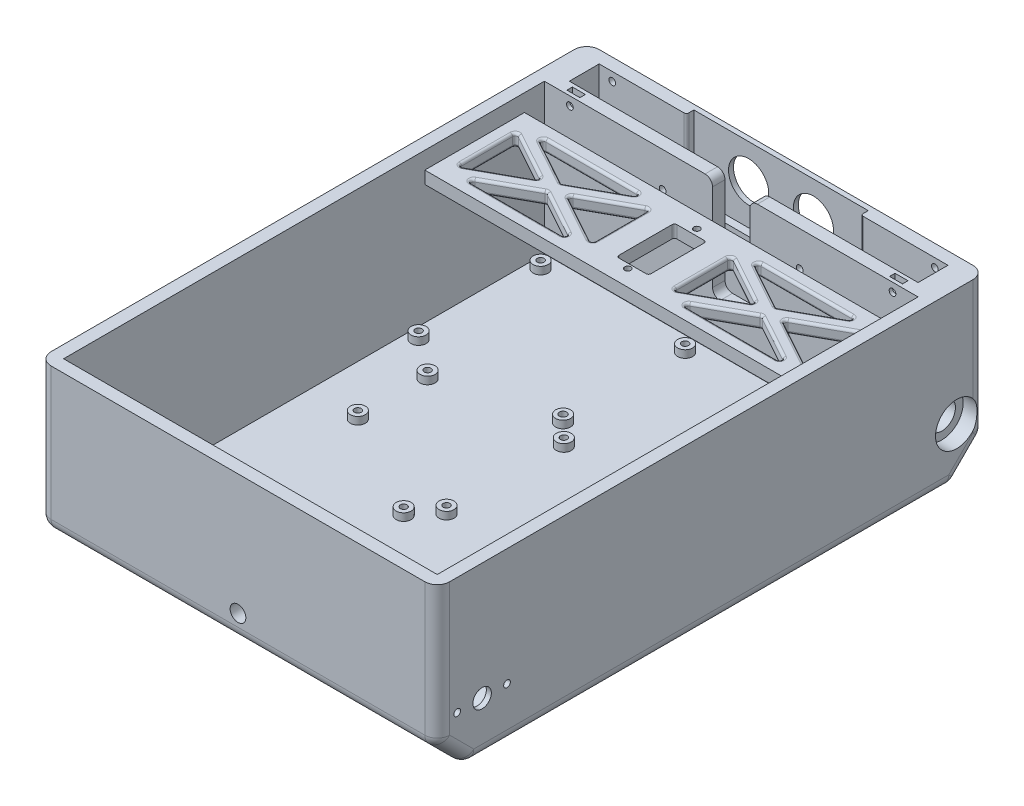
SolidWorks part; units mm, degrees
ref_plane "Front Plane" through (0, 0, 0) normal (0, 0, 1) x (1, 0, 0)
ref_plane "Top Plane" through (0, 0, 0) normal (0, 1, 0) x (1, 0, 0)
ref_plane "Right Plane" through (0, 0, 0) normal (1, 0, 0) x (0, 0, -1)
sketch "Main Body" plane through (0, 0, 0) normal (0, 1, 0) x (1, 0, 0)
  line L0 (-75, 110) -> (75, 110)
  line L1 (-75, -105) -> (75, -105)
  line L2 (-75, -105) -> (-75, 105)
  line L3 (-75, 105) -> (75, 105)
  line L4 (75, -105) -> (75, 105)
  line L5 (-75, -105) -> (75, 105) construction
  line L6 (-75, 105) -> (75, -105) construction
  line L7 (80, -105) -> (80, 105)
  line L8 (-75, -110) -> (75, -110)
  line L9 (-80, -105) -> (-80, 105)
  line L10 (-80, -110) -> (80, -110) construction
  line L11 (-80, -110) -> (-80, 110) construction
  line L12 (80, -110) -> (80, 110) construction
  line L13 (-80, 110) -> (80, 110) construction
  arc A0 (-75, -110) -> (-80, -105) centre (-75, -105) cw
  arc A1 (80, -105) -> (75, -110) centre (75, -105) cw
  arc A2 (75, 110) -> (80, 105) centre (75, 105) cw
  arc A3 (-75, 110) -> (-80, 105) centre (-75, 105) ccw
  point P0 (0, 0)
  dimension "D4" = 5
  dimension "D1" = 75
  dimension "D2" = 210
  dimension "D3" = 5
extrude "Boss-Extrude1" add sketch "Main Body" along normal blind 8 contours L1 L4 L3 L2 | L9 L8 L7 L0 L4 L1 L2 L3 region at (0, 0, -107.2797) region at (0, 0, 0)
extrude "Boss-Extrude3" add sketch "Main Body<4>" along normal blind 60 from surface starting at face at (0, 8, 0)
sketch "Main Body<4>" plane through (0, 0, 0) normal (0, 1, 0) x (1, 0, 0) same geometry as "Main Body"
sketch "Sketch1" plane through (75, 0, 0) normal (-1, 0, 0) x (0, 0, 1)
  line L0 (105, 68) -> (105, 8) construction
  line L1 (-105, 8) -> (105, 8) construction
  line L2 (79, 15.5) -> (105, 15.5)
  line L3 (79, 8) -> (105, 8)
  line L4 (79, 8) -> (79, 34)
  line L5 (79, 34) -> (105, 34)
  line L6 (105, 8) -> (105, 34)
  line L7 (79, 8) -> (105, 34) construction
  line L8 (79, 34) -> (105, 8) construction
  circle A0 centre (92, 21) radius 13
  line M2 (-105, 8) -> (105, 8)
  line M3 (105, 8) -> (105, 68)
  dimension "D1" = 26
  dimension "D2" = 7.5
extrude "Boss-Extrude4" add sketch "Sketch1" along normal up to surface (150 mm away) contours A0 L4 M2 | A0 L3 M3 region at (75, 10.5201, 82.0674) region at (75, 10.5201, 101.9326) up to face at (-75, 38, 0)
sketch "Sketch2" plane through (0, 0, 0) normal (1, 0, 0) x (0, 0, -1)
  line L0 (-105, 68) -> (-105, 15.5) construction
  line L1 (-105, 8) -> (-79, 8)
  line L2 (-105, 8) -> (-105, 15.5)
  line L3 (-105, 15.5) -> (-79, 15.5)
  line L4 (-79, 8) -> (-79, 15.5)
  line L5 (105, 8) -> (-79, 8) construction
  line L6 (-79, 8) -> (-79, 15.5) construction
  line L7 (-79, 15.5) -> (-80.2208, 15.5) construction
extrude "Cut-Extrude1" cut sketch "Sketch2" against normal mid plane 12
sketch "Sketch3" plane through (0, 8, 0) normal (0, 1, 0) x (1, 0, 0)
  line L0 (75, -105) -> (-75, -105) construction
  line L1 (-4, -79) -> (-11, -79)
  line L2 (-4, -79) -> (-4, -105)
  line L3 (-4, -105) -> (-11, -105)
  line L4 (-11, -79) -> (-11, -105)
  line L5 (0, 0) -> (0, -105) construction
  line L6 (-75, -79) -> (-6, -79) construction
  line L7 (11, -79) -> (11, -105)
  line L8 (4, -105) -> (11, -105)
  line L9 (4, -79) -> (4, -105)
  line L10 (4, -79) -> (11, -79)
  line L11 (-6, -103.7792) -> (-6, -92) construction
  dimension "D1" = 5
  dimension "D2" = 4
extrude "Boss-Extrude5" add sketch "Sketch3" along normal blind 20
sketch "Sketch4" plane through (0, 8, 0) normal (0, 1, 0) x (1, 0, 0)
  line L0 (-75, -105) -> (-75, 105) construction
  line L1 (-75, 93) -> (75, 93)
  line L2 (-75, 93) -> (-75, 88)
  line L3 (-75, 88) -> (75, 88)
  line L4 (75, 93) -> (75, 88)
  line L5 (75, 105) -> (75, -105) construction
  line L6 (-75, 105) -> (75, 105) construction
  dimension "D1" = 17
  dimension "D2" = 5
extrude "Boss-Extrude6" add sketch "Sketch4" along normal up to surface (60 mm away) up to face at (0, 68, 0)
sketch "Sketch5" plane through (80, 0, 0) normal (1, 0, 0) x (0, 0, -1)
  circle A0 centre (-92, 21) radius 3.5 construction
  circle A1 centre (-92, 21) radius 3.5
  circle A2 centre (-92, 21) radius 3.7
  dimension "D1" = 0.2
extrude "Cut-Extrude4" cut sketch "Sketch5" against normal up to next contours A1 | A2 A1 region at (80, 21, 92) region at (80, 21, 95.5953)
sketch "Sketch6" plane through (-75, 0, 0) normal (1, 0, 0) x (0, 0, -1)
  circle A0 centre (-92, 21) radius 13
  dimension "D1" = 26
extrude "Cut-Extrude5" cut sketch "Sketch6" against normal offset from surface (3 mm away) 2 up to face at (-80, 34, 0)
mirror "Mirror1" about plane through (0, 0, 0) normal (1, 0, 0) of "Cut-Extrude4"
sketch "Sketch8" plane through (75, 0, 0) normal (-1, 0, 0) x (0, 0, 1)
  circle A0 centre (92, 21) radius 13
  dimension "D1" = 26
extrude "Cut-Extrude6" cut sketch "Sketch8" against normal offset from surface (3 mm away) 2 up to face at (80, 21, 88.3)
sketch "Sketch10" plane through (80, 0, 0) normal (1, 0, 0) x (0, 0, -1)
  circle A1 centre (-82, 21) radius 1.25
  circle A2 centre (-82, 21) radius 1.25
  circle A3 centre (-102, 21) radius 1.25
  circle A4 centre (-102, 21) radius 1.25
  circle A5 centre (-92, 21) radius 12.5
  circle A6 centre (-92, 21) radius 12.5
  circle A63 centre (-102, 21) radius 1.35
  circle A64 centre (-82, 21) radius 1.35
  dimension "D4" = 2.7
extrude "Cut-Extrude7" cut sketch "Sketch10" against normal up to next contours A2 | A64 A2 | A4 | A63 A4 region at (80, 21, 82) region at (80, 21, 102) region at (80, 21, 103.3118) region at (80, 21, 83.3118)
mirror "Mirror3" about plane through (0, 0, 0) normal (1, 0, 0) of "Cut-Extrude7"
sketch "Sketch11" plane through (80, 0, 0) normal (1, 0, 0) x (0, 0, -1)
  circle A0 centre (98.55, 21.05) radius 4.45 construction
  circle A1 centre (98.55, 21.05) radius 4.45
  circle A3 centre (98.55, 21.05) radius 5.45
  dimension "D1" = 1
extrude "Cut-Extrude10" cut sketch "Sketch11" against normal through all contours A1 | A3 A1 region at (80, 21.05, -98.55) region at (80, 21.05, -93.2541)
sketch "Sketch12" plane through (-75, 0, 0) normal (1, 0, 0) x (0, 0, -1)
  line L0 (93, 8) -> (105, 8) construction
  line L1 (93, 68) -> (105, 68)
  line L2 (93, 68) -> (93, 8)
  line L3 (93, 8) -> (105, 8)
  line L4 (105, 68) -> (105, 8)
  line L6 (93, 68) -> (93, 8) construction
  line L7 (93, 68) -> (105, 68) construction
  circle A2 centre (98.55, 21.05) radius 5.45 construction
  circle A3 centre (98.55, 21.05) radius 5.45
extrude "Boss-Extrude7" add sketch "Sketch12" along normal blind 5
sketch "Sketch13" plane through (-80, 0, 0) normal (-1, 0, 0) x (0, 0, 1)
  circle A0 centre (-98.55, 21.05) radius 8.55
  circle A2 centre (-98.55, 21.05) radius 5.45 construction
  dimension "D1" = 17.1
extrude "Cut-Extrude11" cut sketch "Sketch13" against normal blind 6
mirror "Mirror4" about plane through (0, 0, 0) normal (1, 0, 0) of "Boss-Extrude7", "Cut-Extrude11"
sketch "Sketch14" plane through (0, 8, 0) normal (0, 1, 0) x (1, 0, 0)
  line L0 (-4, -105) -> (-4, -79) construction
  line L1 (-4, -95) -> (4, -95)
  line L2 (-4, -95) -> (-4, -105)
  line L3 (-4, -105) -> (4, -105)
  line L4 (4, -95) -> (4, -105)
  dimension "D1" = 10
extrude "Boss-Extrude9" add sketch "Sketch14" along normal blind 5
sketch "Sketch15" plane through (0, 0, 110) normal (0, 0, 1) x (1, 0, 0)
  arc A4 (3.15, 19.5) -> (-3.15, 19.5) centre (0, 19.5) ccw
  arc A5 (-3.15, 19.5) -> (3.15, 19.5) centre (0, 19.5) ccw
  arc A6 (3, 19.5) -> (-3, 19.5) centre (0, 19.5) ccw construction
  dimension "D1" = 3.15
extrude "Cut-Extrude12" cut sketch "Sketch15" against normal up to next contours A4 A5 region at (0, 19.5, 110)
sketch "Sketch16" plane through (0, 0, 0) normal (0, -1, 0) x (1, 0, 0)
  circle A0 centre (-12.5, -82) radius 1.475 construction
  circle A1 centre (-70.5, -82) radius 1.475 construction
  circle A2 centre (-70.5, -33) radius 1.475 construction
  circle A3 centre (-12.5, -33) radius 1.475 construction
  circle A4 centre (-4.2, -25) radius 1.475 construction
  circle A5 centre (-55, -21.12) radius 1.475 construction
  circle A6 centre (-55, 6.88) radius 1.475 construction
  circle A7 centre (-4.2, 22.08) radius 1.475 construction
  circle A8 centre (-12.3, 31.18) radius 1.475 construction
  circle A9 centre (24.2, 31.18) radius 1.475 construction
  circle A10 centre (37.8459, 24.117) radius 1.475 construction
  circle A11 centre (59.5541, 24.117) radius 1.475 construction
  circle A12 centre (59.5541, 68.243) radius 1.475 construction
  circle A13 centre (37.8459, 68.243) radius 1.475 construction
  circle A14 centre (24.2, 67.68) radius 1.475 construction
  circle A15 centre (-12.3, 67.68) radius 1.475 construction
  circle A16 centre (-12.5, -82) radius 1.475
  circle A17 centre (-70.5, -82) radius 1.475
  circle A18 centre (-70.5, -33) radius 1.475
  circle A19 centre (-12.5, -33) radius 1.475
  circle A20 centre (-4.2, -25) radius 1.475
  circle A21 centre (-55, -21.12) radius 1.475
  circle A22 centre (-55, 6.88) radius 1.475
  circle A23 centre (-4.2, 22.08) radius 1.475
  circle A24 centre (-12.3, 31.18) radius 1.475
  circle A25 centre (24.2, 31.18) radius 1.475
  circle A26 centre (37.8459, 24.117) radius 1.475
  circle A27 centre (59.5541, 24.117) radius 1.475
  circle A28 centre (59.5541, 68.243) radius 1.475
  circle A29 centre (37.8459, 68.243) radius 1.475
  circle A30 centre (24.2, 67.68) radius 1.475
  circle A31 centre (-12.3, 67.68) radius 1.475
  circle A32 centre (-70.5, -82) radius 1.35
  circle A33 centre (-12.5, -82) radius 1.35
  circle A34 centre (-12.5, -33) radius 1.35
  circle A35 centre (-4.2, -25) radius 1.35
  circle A36 centre (-55, -21.12) radius 1.35
  circle A37 centre (-70.5, -33) radius 1.35
  circle A38 centre (-55, 6.88) radius 1.35
  circle A39 centre (-12.3, 31.18) radius 1.35
  circle A40 centre (-4.2, 22.08) radius 1.35
  circle A41 centre (24.2, 31.18) radius 1.35
  circle A42 centre (37.8459, 24.117) radius 1.35
  circle A43 centre (59.5541, 24.117) radius 1.35
  circle A44 centre (37.8459, 68.243) radius 1.35
  circle A45 centre (59.5541, 68.243) radius 1.35
  circle A46 centre (24.2, 67.68) radius 1.35
  circle A47 centre (-12.3, 67.68) radius 1.35
  dimension "D1" = 2.7
extrude "Cut-Extrude13" cut sketch "Sketch16" against normal up to next contours A47 | A46 | A44 | A45 | A35 | A37 | A36 | A38 | A39 | A40 | A41 | A42 | A43 | A32 | A33 | A19 region at (-70.5, 0, -82) region at (-12.5, 0, -82) region at (-4.2, 0, -25) region at (-55, 0, -21.12) region at (-70.5, 0, -33) region at (-55, 0, 6.88) region at (-12.3, 0, 31.18) region at (-4.2, 0, 22.08) region at (24.2, 0, 31.18) region at (37.8459, 0, 24.117) region at (59.5541, 0, 24.117) region at (37.8459, 0, 68.243) region at (59.5541, 0, 68.243) region at (24.2, 0, 67.68) region at (-12.3, 0, 67.68)
sketch "Sketch18" plane through (75, 0, 0) normal (-1, 0, 0) x (0, 0, 1)
  line L1 (-80, 61.1) -> (-40, 61.1)
  line L2 (-80, 61.1) -> (-80, 56.1)
  line L3 (-80, 56.1) -> (-40, 56.1)
  line L4 (-40, 61.1) -> (-40, 56.1)
  line L5 (-88, 68) -> (105, 68) construction
  dimension "D1" = 5
  dimension "D2" = 30
  dimension "D3" = 40
  dimension "D4" = 6.9
extrude "Boss-Extrude11" add sketch "Sketch18" along normal up to next
sketch "Sketch19" plane through (0, 68, 0) normal (0, 1, 0) x (1, 0, 0)
  line L1 (-6.425, 71.625) -> (6.425, 71.625)
  line L2 (-6.425, 71.625) -> (-6.425, 48.375)
  line L3 (-6.425, 48.375) -> (6.425, 48.375)
  line L4 (6.425, 71.625) -> (6.425, 48.375)
  line L12 (-75, 80) -> (-75, 40)
  line L13 (-75, 40) -> (75, 40)
  line L14 (75, 40) -> (75, 80)
  line L15 (75, 80) -> (-75, 80)
  line L16 (-75, 80) -> (-75, 40)
  line L17 (-75, 40) -> (75, 40)
  line L18 (75, 40) -> (75, 80)
  line L19 (75, 80) -> (-75, 80)
  point P4 (0, 71.625)
  point P8 (0, 80)
  point P12 (6.425, 60)
  point P13 (75, 60)
  dimension "D1" = 23.25
  dimension "D2" = 12.85
  dimension "D3" = 0
extrude "Cut-Extrude14" cut sketch "Sketch19" against normal up to next contours L4 L1 L2 L3 region at (0, 68, -60)
sketch "Sketch21" plane through (0, 0, -110) normal (0, 0, -1) x (-1, 0, 0)
  circle A1 centre (-64.75, 64.5) radius 1.3
  circle A2 centre (-64.75, 64.5) radius 1.3
  circle A3 centre (64.75, 64.5) radius 1.3
  circle A4 centre (64.75, 64.5) radius 1.3
  circle A44 centre (-64.75, 64.5) radius 1.35
  circle A45 centre (64.75, 64.5) radius 1.35
  dimension "D3" = 2.7
extrude "Cut-Extrude16" cut sketch "Sketch21" against normal up to surface (22 mm away) contours A44 A2 | A2 | A45 A4 | A4 region at (64.75, 64.5, -110) region at (-64.75, 64.5, -110) region at (66.0618, 64.5, -110) region at (-63.4382, 64.5, -110) up to face at (0, 38, -88)
ref_plane "Plane1" through (0, 0, -90.5) normal (0, 0, -1) x (-1, 0, 0)
sketch "Sketch22" plane through (0, 0, -90.5) normal (0, 0, -1) x (-1, 0, 0)
  line L0 (-67.35, 66.0011) -> (-67.35, 68)
  line L1 (-62.15, 66.0011) -> (-64.75, 67.5022)
  line L2 (-64.75, 67.5022) -> (-67.35, 66.0011)
  line L3 (-67.35, 66.0011) -> (-67.35, 62.9989)
  line L4 (-67.35, 62.9989) -> (-64.75, 61.4978)
  line L5 (-64.75, 61.4978) -> (-62.15, 62.9989)
  line L6 (-62.15, 62.9989) -> (-62.15, 66.0011)
  line L7 (-67.35, 68) -> (-62.15, 68)
  line L8 (-62.15, 68) -> (-62.15, 66.0011)
  line L9 (70, 68) -> (-70, 68) construction
  line L10 (0, 0) -> (0, 68) construction
  line L11 (75, 68) -> (-75, 68) construction
  line L12 (64.75, 61.4978) -> (62.15, 62.9989)
  line L13 (67.35, 62.9989) -> (64.75, 61.4978)
  line L14 (64.75, 67.5022) -> (67.35, 66.0011)
  line L15 (67.35, 66.0011) -> (67.35, 62.9989)
  line L16 (67.35, 66.0011) -> (67.35, 68)
  line L17 (62.15, 62.9989) -> (62.15, 66.0011)
  line L18 (62.15, 68) -> (62.15, 66.0011)
  line L19 (67.35, 68) -> (62.15, 68)
  line L20 (62.15, 66.0011) -> (64.75, 67.5022)
  circle A0 centre (-64.75, 64.5) radius 2.6 construction
  circle A1 centre (-64.75, 64.5) radius 1.35 construction
  dimension "D1" = 5.2
extrude "Cut-Extrude17" cut sketch "Sketch22" against normal mid plane 2.2 contours L20 L17 L12 L13 L15 L14 | L18 L20 L14 L16 L19 | L5 L6 L1 L2 L3 L4 | L8 L7 L0 L2 L1 region at (67.2943, 67.0006, -90.5) region at (64.75, 64.5, -90.5) region at (-64.75, 64.5, -90.5) region at (-62.2057, 67.0006, -90.5)
sketch "Sketch23" plane through (0, 0, -110) normal (0, 0, -1) x (-1, 0, 0)
  circle A0 centre (64.75, 64.5) radius 2.5
  circle A1 centre (-64.75, 64.5) radius 2.5
  circle A2 centre (64.75, 64.5) radius 1.35 construction
  circle A3 centre (-64.75, 64.5) radius 1.35 construction
  dimension "D1" = 5
  dimension "D2" = 5
extrude "Cut-Extrude18" cut sketch "Sketch23" against normal mid plane 2.5
sketch "Sketch24" plane through (0, 61.1, 0) normal (0, 1, 0) x (1, 0, 0)
  circle A0 centre (0, 46.475) radius 1.2502
  arc A1 (0.4, 45.5583) -> (-0.4, 45.5583) centre (0, 46.475) ccw construction
  circle A2 centre (0, 74.175) radius 1.2502
  arc A3 (-0.4, 75.0917) -> (0, 73.1748) centre (0, 74.175) ccw construction
  point P5 (0.4, 45.5583)
  dimension "D1" = 0.25
extrude "Cut-Extrude19" cut sketch "Sketch24" against normal up to next
sketch "Sketch25" plane through (0, 61.1, 0) normal (0, 1, 0) x (1, 0, 0)
  line L1 (-11.3, 80) -> (11.3, 80)
  line L2 (-11.3, 80) -> (-11.3, 40)
  line L3 (-11.3, 40) -> (11.3, 40)
  line L4 (-75, 80) -> (-75, 40)
  line L5 (-75, 40) -> (75, 40)
  line L6 (75, 40) -> (75, 80)
  line L7 (75, 80) -> (-75, 80)
  line L8 (-75, 80) -> (-75, 40)
  line L9 (-75, 40) -> (75, 40)
  line L10 (75, 40) -> (75, 80)
  line L11 (75, 80) -> (-75, 80)
  line L12 (11.3, 80) -> (11.3, 40)
  line L13 (-11.3, 80) -> (11.3, 40) construction
  line L14 (-11.3, 40) -> (11.3, 80) construction
  line L15 (0, 80) -> (0, 40) construction
  line L16 (70, 75) -> (70, 45)
  line L17 (-70, 75) -> (-16.3, 75)
  line L18 (-70, 75) -> (-70, 45)
  line L19 (-70, 45) -> (-16.3, 45)
  line L20 (-16.3, 75) -> (-16.3, 45)
  line L21 (-70, 75) -> (-16.3, 45) construction
  line L22 (-70, 45) -> (-16.3, 75) construction
  line L23 (70, 75) -> (16.3, 45) construction
  line L24 (70, 45) -> (16.3, 75) construction
  line L25 (70, 75) -> (16.3, 75)
  line L26 (16.3, 75) -> (16.3, 45)
  line L27 (70, 45) -> (16.3, 45)
  line L28 (-75, 60) -> (-11.3, 60) construction
  line L29 (75, 60) -> (11.3, 60) construction
  line L30 (-70, 71.9362) -> (-48.3314, 60)
  line L31 (-16.3, 71.9362) -> (-37.9686, 60)
  line L32 (70, 71.9362) -> (48.3314, 60)
  line L33 (-48.3314, 60) -> (-70, 48.0638)
  line L34 (48.3314, 60) -> (70, 48.0638)
  line L35 (-65.199, 45) -> (-43.15, 57.1458)
  line L36 (65.199, 45) -> (43.15, 57.1458)
  line L37 (-43.15, 57.1458) -> (-21.101, 45)
  line L38 (43.15, 57.1458) -> (21.101, 45)
  line L39 (16.3, 71.9362) -> (37.9686, 60)
  line L40 (-37.9686, 60) -> (-16.3, 48.0638)
  line L41 (37.9686, 60) -> (16.3, 48.0638)
  line L42 (-65.199, 75) -> (-43.15, 62.8542)
  line L43 (65.199, 75) -> (43.15, 62.8542)
  line L44 (-43.15, 62.8542) -> (-21.101, 75)
  line L45 (43.15, 62.8542) -> (21.101, 75)
  line L46 (-75, 40) -> (-75, 80) construction
  line L47 (-75, 40) -> (75, 40) construction
  point P2 (0, 60)
  point P9 (-43.15, 60)
  point P10 (75, 60)
  point P24 (43.15, 60)
  point P62 (-54.1745, 68.9271)
  dimension "D2" = 150
  dimension "D3" = 5
  dimension "D4" = 5
  dimension "D5" = 5
  dimension "D6" = 26.6686
  dimension "D7" = 140.199
  dimension "D1" = 0
extrude "Cut-Extrude21" cut sketch "Sketch25" against normal up to next contours L37 L35 L19 | L33 L30 L18 | L42 L44 L17 | L31 L40 L20 | L41 L39 L26 | L45 L43 L25 | L36 L38 L27 | L32 L34 L16 region at (62.7771, 61.1, -60) region at (43.15, 61.1, -70.9514) region at (43.15, 61.1, -49.0486) region at (23.5229, 61.1, -60) region at (-43.15, 61.1, -70.9514) region at (-62.7771, 61.1, -60) region at (-23.5229, 61.1, -60) region at (-43.15, 61.1, -49.0486)
sketch "Sketch26" plane through (-80, 0, 0) normal (-1, 0, 0) x (0, 0, 1)
  line L0 (-110, 12.58) -> (-97.42, 0)
  line L1 (-110, 68) -> (-110, 0) construction
  line L2 (105, 0) -> (-105, 0) construction
  line L3 (-97.42, 0) -> (-92.42, 0)
  line L4 (-92.42, 0) -> (-110, 17.58)
  line L5 (-110, 17.58) -> (-110, 12.58)
  line L6 (-110, 12.58) -> (-110, 0)
  line L7 (-110, 0) -> (-97.42, 0)
  circle A1 centre (-98.55, 21.05) radius 8.55 construction
  line M5 (-105, 15.4375) -> (-105, 0)
  line M6 (-105, 0) -> (105, 0)
  dimension "D1" = 2
  dimension "D2" = 5
  dimension "D3" = 45
extrude "Cut-Extrude22" cut sketch "Sketch26" against normal up to next contours L6 L7 L0 M5 | L0 M5 M6 region at (-80, 5.1434, -107.7067) region at (-80, 2.5267, -102.4733)
mirror "Mirror5" about plane through (0, 0, 0) normal (0, 0, 1) of "Cut-Extrude22"
fillet "Fillet1" radius 5 14 edges at (80, 3.79, -101.21) (78.5355, 11.1156, -108.5355) (-80, 3.79, -101.21) (-78.5355, 11.1156, -108.5355) (80, 3.79, 101.21) (78.5355, 11.1156, 108.5355) (-80, 3.79, 101.21) (-78.5355, 11.1156, 108.5355) (0, 0, -97.42) (0, 12.58, -110) (0, 0, 97.42) (0, 12.58, 110) (-80, 0, 0) (80, 0, 0)
fillet "Fillet2" radius 1 76 edges at (-32.1255, 56.1, -51.0729) (-32.1255, 61.1, -51.0729) (-21.101, 58.6, -45) (-43.15, 61.1, -45) (-43.15, 56.1, -45) (-54.1745, 56.1, -51.0729) (-65.199, 58.6, -45) (-54.1745, 61.1, -51.0729) (-43.15, 58.6, -57.1458) (32.1255, 56.1, -68.9271) (32.1255, 61.1, -68.9271) (21.101, 58.6, -75) (43.15, 61.1, -75) (43.15, 56.1, -75) (54.1745, 56.1, -68.9271) (65.199, 58.6, -75) (54.1745, 61.1, -68.9271) (43.15, 58.6, -62.8542) (54.1745, 61.1, -51.0729) (54.1745, 56.1, -51.0729) (43.15, 56.1, -45) (65.199, 58.6, -45) (43.15, 61.1, -45) (21.101, 58.6, -45) (32.1255, 61.1, -51.0729) (43.15, 58.6, -57.1458) (32.1255, 56.1, -51.0729) (59.1657, 61.1, -65.9681) (59.1657, 56.1, -65.9681) (70, 56.1, -60) (70, 58.6, -71.9362) (70, 61.1, -60) (70, 58.6, -48.0638) (59.1657, 61.1, -54.0319) (48.3314, 58.6, -60) (59.1657, 56.1, -54.0319) (-54.1745, 61.1, -68.9271) (-54.1745, 56.1, -68.9271) (-43.15, 56.1, -75) (-65.199, 58.6, -75) (-43.15, 61.1, -75) (-21.101, 58.6, -75) (-32.1255, 61.1, -68.9271) (-43.15, 58.6, -62.8542) (-32.1255, 56.1, -68.9271) (-59.1657, 56.1, -54.0319) (-59.1657, 61.1, -54.0319) (-70, 58.6, -48.0638) (-70, 61.1, -60) (-70, 56.1, -60) (-59.1657, 56.1, -65.9681) (-70, 58.6, -71.9362) (-59.1657, 61.1, -65.9681) (-48.3314, 58.6, -60) (-27.1343, 61.1, -65.9681) (-27.1343, 56.1, -65.9681) (-16.3, 56.1, -60) (-16.3, 58.6, -71.9362) (-16.3, 61.1, -60) (-16.3, 58.6, -48.0638) (-27.1343, 61.1, -54.0319) (-37.9686, 58.6, -60) (-27.1343, 56.1, -54.0319) (27.1343, 56.1, -54.0319) (27.1343, 61.1, -54.0319) (16.3, 58.6, -48.0638) (16.3, 61.1, -60) (16.3, 56.1, -60) (27.1343, 56.1, -65.9681) (16.3, 58.6, -71.9362) (27.1343, 61.1, -65.9681) (37.9686, 58.6, -60) (6.425, 58.6, -48.375) (-6.425, 58.6, -48.375) (-6.425, 58.6, -71.625) (6.425, 58.6, -71.625)
sketch "Sketch33" plane through (0, 0, -110) normal (0, 0, -1) x (-1, 0, 0)
  circle A0 centre (-13, 53.9999) radius 8.075
  circle A1 centre (13, 53.9999) radius 8.075
  circle A2 centre (-13, 53.9999) radius 7.3 construction
  circle A3 centre (13, 53.9999) radius 7.3 construction
  dimension "D1" = 16.15
extrude "Cut-Extrude27" cut sketch "Sketch33" against normal up to next
sketch "Sketch34" plane through (0, 0, -93) normal (0, 0, -1) x (-1, 0, 0)
  circle A0 centre (27.525, 54) radius 1.35 construction
  circle A1 centre (27.525, 54) radius 1.35
  circle A2 centre (-27.525, 54) radius 1.35 construction
  circle A3 centre (-27.525, 54) radius 1.35
  circle A4 centre (-27.525, 54) radius 1.35
  circle A5 centre (27.525, 54) radius 1.35
  dimension "D1" = 2.7
  dimension "D2" = 2.7
extrude "Cut-Extrude28" cut sketch "Sketch34" against normal up to next contours A3 | A1 region at (-27.525, 54, -93) region at (27.525, 54, -93)
sketch "Sketch35" plane through (0, 68, 0) normal (0, 1, 0) x (1, 0, 0)
  line L0 (70, 93) -> (-70, 93) construction
  line L1 (-7.5, 93) -> (7.5, 93)
  line L2 (-7.5, 93) -> (-7.5, 88)
  line L3 (-7.5, 88) -> (7.5, 88)
  line L4 (7.5, 93) -> (7.5, 88)
  line L5 (-7.5, 93) -> (7.5, 88) construction
  line L6 (-7.5, 88) -> (7.5, 93) construction
  line L7 (-75, 88) -> (75, 88) construction
  point P0 (0, 90.5)
  dimension "D1" = 15
extrude "Cut-Extrude29" cut sketch "Sketch35" against normal offset from surface (41 mm away) 19 up to face at (-4.2, 8, -23.65)
fillet "Fillet4" radius 3 9 edges at (0, 8, 95) (-7.5, 28, 79) (-7.5, 28, 105) (7.5, 28, 105) (7.5, 28, 79) (-7.5, 68, -90.5) (7.5, 68, -90.5) (-7.5, 27, -90.5) (7.5, 27, -90.5)
fillet "Fillet5" radius 1 1 edges at (0, 13, 95)
sketch "Sketch36" plane through (0, 68, 0) normal (0, 1, 0) x (1, 0, 0)
  line L0 (-70, 105) -> (70, 105) construction
  line L1 (-35, 108) -> (35, 108)
  line L2 (-35, 108) -> (-35, 105)
  line L3 (-35, 105) -> (35, 105)
  line L4 (35, 108) -> (35, 105)
  line L5 (-75, 110) -> (75, 110) construction
  point P6 (0, 108)
  dimension "D1" = 70
  dimension "D2" = 2
extrude "Cut-Extrude30" cut sketch "Sketch36" against normal blind 30
fillet "Fillet6" radius 1 2 edges at (35, 53, -105) (-35, 53, -105)
sketch "Sketch37" plane through (0, 8, 0) normal (0, 1, 0) x (1, 0, 0)
  line L8 (-4, -79) -> (-4, -92)
  line L9 (-4, -92) -> (4, -92)
  line L10 (4, -92) -> (4, -79)
  line L11 (4, -79) -> (75, -79)
  line L12 (75, -79) -> (75, 88)
  line L13 (75, 88) -> (-75, 88)
  line L14 (-75, 88) -> (-75, -79)
  line L15 (-75, -79) -> (-4, -79)
  line L16 (-4, -79) -> (-4, -92)
  line L17 (-4, -92) -> (4, -92)
  line L18 (4, -92) -> (4, -79)
  line L19 (4, -79) -> (75, -79)
  line L20 (75, -79) -> (75, 88)
  line L21 (75, 88) -> (-75, 88)
  line L22 (-75, 88) -> (-75, -79)
  line L23 (-75, -79) -> (-4, -79)
  circle A0 centre (-12.5, 82) radius 1.35 construction
  circle A1 centre (-4.2, 25) radius 1.35 construction
  circle A2 centre (-12.5, 33) radius 1.475 construction
  circle A3 centre (-70.5, 33) radius 1.35 construction
  circle A4 centre (-55, 21.12) radius 1.35 construction
  circle A5 centre (-55, -6.88) radius 1.35 construction
  circle A6 centre (-12.3, -31.18) radius 1.35 construction
  circle A7 centre (-4.2, -22.08) radius 1.35 construction
  circle A8 centre (24.2, -31.18) radius 1.35 construction
  circle A9 centre (37.8459, -24.117) radius 1.35 construction
  circle A10 centre (59.5541, -24.117) radius 1.35 construction
  circle A11 centre (59.5541, -68.243) radius 1.35 construction
  circle A12 centre (37.8459, -68.243) radius 1.35 construction
  circle A13 centre (24.2, -67.68) radius 1.35 construction
  circle A14 centre (-12.3, -67.68) radius 1.35 construction
  circle A15 centre (-70.5, 82) radius 1.35 construction
  circle A16 centre (-12.5, 82) radius 1.35
  circle A17 centre (-4.2, 25) radius 1.35
  circle A18 centre (-12.5, 33) radius 1.475
  circle A19 centre (-70.5, 33) radius 1.35
  circle A20 centre (-55, 21.12) radius 1.35
  circle A21 centre (-55, -6.88) radius 1.35
  circle A22 centre (-12.3, -31.18) radius 1.35
  circle A23 centre (-4.2, -22.08) radius 1.35
  circle A24 centre (24.2, -31.18) radius 1.35
  circle A25 centre (37.8459, -24.117) radius 1.35
  circle A26 centre (59.5541, -24.117) radius 1.35
  circle A27 centre (59.5541, -68.243) radius 1.35
  circle A28 centre (37.8459, -68.243) radius 1.35
  circle A29 centre (24.2, -67.68) radius 1.35
  circle A30 centre (-12.3, -67.68) radius 1.35
  circle A31 centre (-70.5, 82) radius 1.35
  circle A32 centre (-12.3, -67.68) radius 3
  circle A33 centre (24.2, -67.68) radius 3
  circle A34 centre (37.8459, -68.243) radius 3
  circle A35 centre (59.5541, -68.243) radius 3
  circle A36 centre (24.2, -31.18) radius 3
  circle A37 centre (37.8459, -24.117) radius 3
  circle A38 centre (59.5541, -24.117) radius 3
  circle A39 centre (-4.2, -22.08) radius 3
  circle A40 centre (-12.3, -31.18) radius 3
  circle A41 centre (-4.2, 25) radius 3
  circle A42 centre (-55, -6.88) radius 3
  circle A43 centre (-55, 21.12) radius 3
  circle A44 centre (-12.5, 33) radius 3
  circle A45 centre (-12.5, 82) radius 3
  circle A46 centre (-70.5, 82) radius 3
  circle A47 centre (-70.5, 33) radius 3
  circle M9 centre (-4.2, 25) radius 1.35
  circle M10 centre (59.5541, -68.243) radius 1.35
  circle M11 centre (37.8459, -68.243) radius 1.35
  circle M12 centre (24.2, -67.68) radius 1.35
  circle M13 centre (-70.5, 33) radius 1.35
  circle M14 centre (-55, 21.12) radius 1.35
  circle M15 centre (-55, -6.88) radius 1.35
  circle M16 centre (-12.3, -31.18) radius 1.35
  circle M17 centre (-4.2, -22.08) radius 1.35
  circle M18 centre (24.2, -31.18) radius 1.35
  circle M19 centre (37.8459, -24.117) radius 1.35
  circle M20 centre (59.5541, -24.117) radius 1.35
  circle M21 centre (-70.5, 82) radius 1.35
  circle M22 centre (-12.5, 82) radius 1.35
  circle M23 centre (-12.5, 33) radius 1.475
  circle M24 centre (-12.3, -67.68) radius 1.35
  dimension "D2" = 6
  dimension "D1" = 0
extrude "Boss-Extrude12" add sketch "Sketch37" along normal blind 3 contours A46 M21 | A45 M22 | A44 M23 | A41 M9 | A47 M13 | A43 M14 | A42 M15 | A38 M20 | A35 M10 | A34 M11 | A37 M19 | A36 M18 | A33 M12 | A39 M17 | A40 M16 | A32 M24 region at (-15.2151, 8, 67.68) region at (21.2849, 8, 67.68) region at (34.9307, 8, 68.243) region at (56.639, 8, 68.243) region at (21.2849, 8, 31.18) region at (34.9307, 8, 24.117) region at (56.639, 8, 24.117) region at (-7.1151, 8, 22.08) region at (-15.2151, 8, 31.18) region at (-7.1151, 8, -25) region at (-57.9151, 8, 6.88) region at (-57.9151, 8, -21.12) region at (-15.4151, 8, -33) region at (-15.4151, 8, -82) region at (-73.4151, 8, -82) region at (-73.4151, 8, -33)
equation "\"Screw\"= 2.7"
equation "\"D1@Sketch16\"=\"Screw\""
equation "\"D4@Sketch10\"=\"Screw\""
equation "\"D3@Sketch21\"=\"Screw\""
equation "\"D2@Sketch34\"=\"Screw\""
equation "\"D1@Sketch34\"=\"Screw\""
